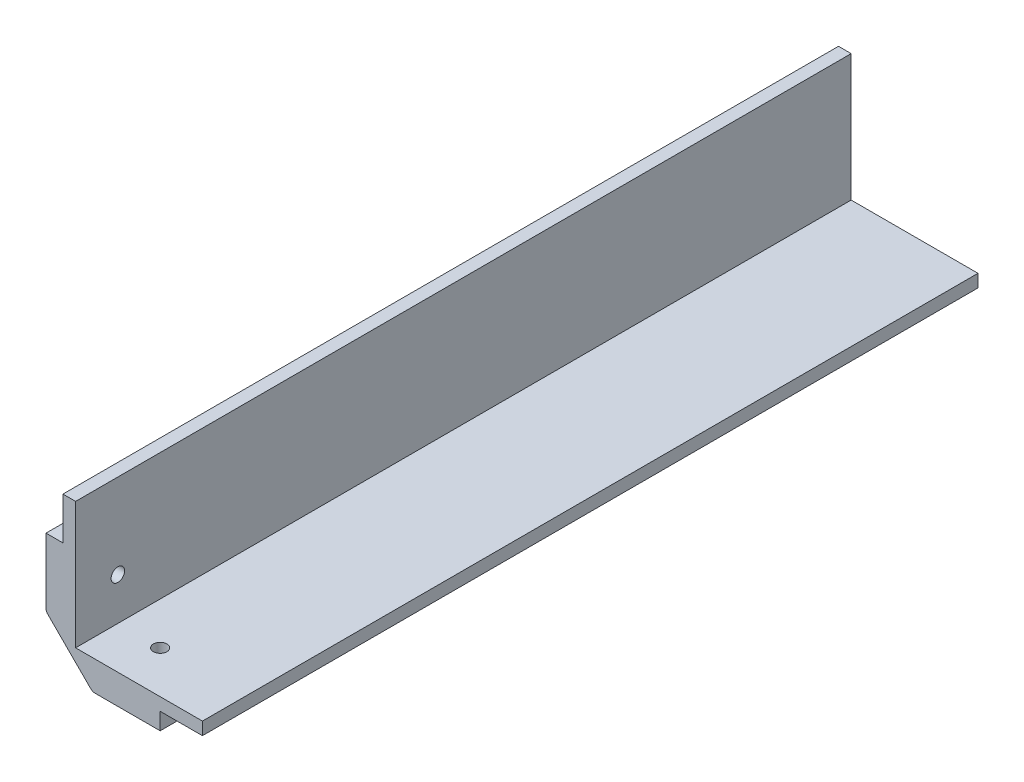
SolidWorks part; units mm, degrees
ref_plane "Front Plane" through (0, 0, 0) normal (0, 0, 1) x (1, 0, 0)
ref_plane "Top Plane" through (0, 0, 0) normal (0, 1, 0) x (1, 0, 0)
ref_plane "Right Plane" through (0, 0, 0) normal (1, 0, 0) x (0, 0, -1)
ref_plane "Plane1" through (0, 0, 280) normal (0, 0, 1) x (1, 0, 0)
sketch "Sketch1" plane through (0, 0, 280) normal (0, 0, 1) x (1, 0, 0)
  line L0 (-7, 4) -> (4, -7)
  line L1 (4, -7) -> (7, -7)
  line L2 (7, -7) -> (7, -3)
  line L3 (7, -3) -> (20, -3)
  line L4 (20, -3) -> (20, 0)
  line L5 (20, 0) -> (0, 0)
  line L6 (0, 0) -> (0, 20)
  line L7 (0, 20) -> (-3, 20)
  line L8 (-3, 20) -> (-3, 7)
  line L9 (-3, 7) -> (-7, 7)
  line L10 (-7, 7) -> (-7, 4)
extrude "Boss-Extrude1" add sketch "Sketch1" against normal blind 183.45
fillet "Fillet1" radius 1.5 2 edges at (-7, 4, 188.275) (4, -7, 188.275)
sketch "Sketch7" plane through (0, -3, 0) normal (0, -1, 0) x (1, 0, 0)
  line L2 (7, 96.55) -> (20, 96.55) construction
  line L3 (20, 96.55) -> (20, 280) construction
  line L10 (7, 96.55) -> (7, 280) construction
  line L12 (7, 280) -> (20, 280) construction
  line L13 (7, 96.55) -> (20, 96.55)
  line L14 (7, 96.55) -> (7, 280)
  line L16 (20, 96.55) -> (20, 280)
  line L17 (7, 280) -> (20, 280)
  point P0 (0, 0)
sketch "Sketch6" plane through (20, 0, 0) normal (1, 0, 0) x (0, 0, -1)
  line L4 (-280, 0) -> (-280, -3)
  line L5 (-280, -3) -> (-96.55, -3)
  line L6 (-96.55, -3) -> (-96.55, 0)
  line L7 (-96.55, 0) -> (-280, 0)
  line L8 (-280, 0) -> (-280, -3)
  line L9 (-280, -3) -> (-96.55, -3)
  line L10 (-96.55, -3) -> (-96.55, 0)
  line L11 (-96.55, 0) -> (-280, 0)
  dimension "D1" = 0
extrude "Boss-Extrude2" add sketch "Sketch6" along normal blind 10
extrude "Boss-Extrude3" add sketch "Sketch7" along normal up to surface (4 mm away) up to face at (5.8107, -7, 188.275)
sketch "Sketch9" plane through (-3, 0, 0) normal (-1, 0, 0) x (0, 0, 1)
  line L4 (280, 7) -> (280, 20)
  line L5 (280, 20) -> (96.55, 20)
  line L6 (96.55, 20) -> (96.55, 7)
  line L7 (96.55, 7) -> (280, 7)
  line L8 (280, 7) -> (280, 20)
  line L9 (280, 20) -> (96.55, 20)
  line L10 (96.55, 20) -> (96.55, 7)
  line L11 (96.55, 7) -> (280, 7)
  dimension "D1" = 0
sketch "Sketch8" plane through (0, 20, 0) normal (0, 1, 0) x (1, 0, 0)
  line L4 (-3, -280) -> (0, -280)
  line L5 (0, -280) -> (0, -96.55)
  line L6 (0, -96.55) -> (-3, -96.55)
  line L7 (-3, -96.55) -> (-3, -280)
  line L8 (-3, -280) -> (0, -280)
  line L9 (0, -280) -> (0, -96.55)
  line L10 (0, -96.55) -> (-3, -96.55)
  line L11 (-3, -96.55) -> (-3, -280)
  dimension "D1" = 0
extrude "Boss-Extrude4" add sketch "Sketch8" along normal blind 10
extrude "Boss-Extrude5" add sketch "Sketch9" along normal up to surface (4 mm away) up to face at (-7, 5.8107, 188.275)
sketch "Sketch10" plane through (0, -7, 0) normal (0, -1, 0) x (1, 0, 0)
  line L0 (10, 270) -> (10, 106.55) construction
  line L1 (20, 96.55) -> (20, 280) construction
  line L2 (55, 280) -> (-55, 280) construction
  line L3 (4.6213, 96.55) -> (20, 96.55) construction
  point P0 (10, 270)
  dimension "D1" = 10
  dimension "D2" = 10
  dimension "D3" = 10
hole_wizard "CSK for M3 SFHCS1" positions "Sketch10" profile "Sketch11" countersink size "M3" standard "ANSI Metric" end condition through all
sketch "Sketch11" plane through (10, -7, 270) normal (1, 0, 0) x (0, 0, -1)
  line L0 (0, 0) -> (0, 37)
  line L1 (0, 37) -> (1.6, 37)
  line L2 (1.6, 37) -> (1.6, 1.76)
  line L3 (1.6, 1.76) -> (3.36, 0)
  line L5 (3.36, 0) -> (0, 0)
  line L6 (-1.6, 1.76) -> (-3.36, 0) construction
  line L11 (0, -6.35) -> (0, 107.95) construction
  dimension "Thru Hole Dia." = 3.2
  dimension "Thru Hole Depth" = 37
  dimension "Near C'Sink Dia." = 6.72
  dimension "Near C'Sink Angle" = 90
sketch "Sketch12" plane through (-7, 0, 0) normal (-1, 0, 0) x (0, 0, 1)
  line L0 (106.55, 10) -> (270, 10) construction
  line L1 (280, 20) -> (280, 4.6213) construction
  line L2 (280, 20) -> (96.55, 20) construction
  line L3 (96.55, 20) -> (96.55, 4.6213) construction
  point P1 (270, 10)
  dimension "D1" = 10
  dimension "D2" = 10
  dimension "D3" = 10
hole_wizard "CSK for M3 SFHCS2" positions "Sketch12" profile "Sketch13" countersink size "M3" standard "ANSI Metric" end condition through all
sketch "Sketch13" plane through (-7, 10, 270) normal (0, 1, 0) x (0, 0, 1)
  line L0 (0, 0) -> (0, 37)
  line L1 (0, 37) -> (1.6, 37)
  line L2 (1.6, 37) -> (1.6, 1.76)
  line L3 (1.6, 1.76) -> (3.36, 0)
  line L5 (3.36, 0) -> (0, 0)
  line L6 (-1.6, 1.76) -> (-3.36, 0) construction
  line L11 (0, -6.35) -> (0, 107.95) construction
  dimension "Thru Hole Dia." = 3.2
  dimension "Thru Hole Depth" = 37
  dimension "Near C'Sink Dia." = 6.72
  dimension "Near C'Sink Angle" = 90
